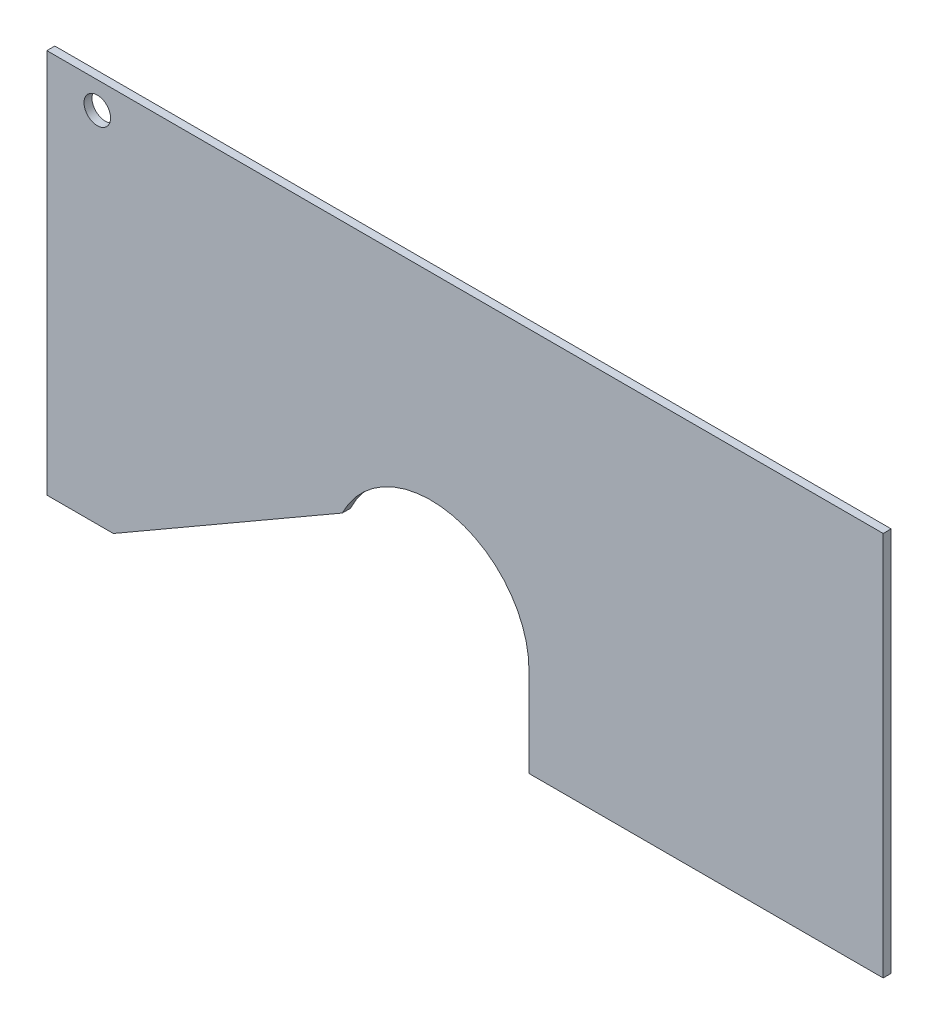
SolidWorks part; units mm, degrees
ref_plane "Front Plane" through (0, 0, 0) normal (0, 0, 1) x (1, 0, 0)
ref_plane "Top Plane" through (0, 0, 0) normal (0, 1, 0) x (1, 0, 0)
ref_plane "Right Plane" through (0, 0, 0) normal (1, 0, 0) x (0, 0, -1)
sketch "Sketch2" plane through (0, 0, 0) normal (0, 0, 1) x (1, 0, 0)
  line L0 (25.0304, 0) -> (111.2865, 49.8)
  line L1 (0, 0) -> (25.0304, 0)
  line L2 (0, 0) -> (0, 145)
  line L3 (0, 145) -> (315, 145)
  line L4 (315, 0) -> (315, 145)
  line L5 (181.6, 33.7) -> (181.6, 0)
  line L6 (181.6, 0) -> (315, 0)
  circle A0 centre (19, 135) radius 5
  arc A1 (181.6, 33.7) -> (111.2865, 49.8) centre (144.6, 33.7) ccw
  dimension "D3" = 135
  dimension "D4" = 19
  dimension "D5" = 10
  dimension "D6" = 74
  dimension "D7" = 170.4
  dimension "D8" = 33.7
  dimension "D1" = 315
  dimension "D2" = 145
  dimension "D9" = 30
  dimension "D10" = 99.6
extrude "Boss-Extrude2" add sketch "Sketch2" along normal blind 3
